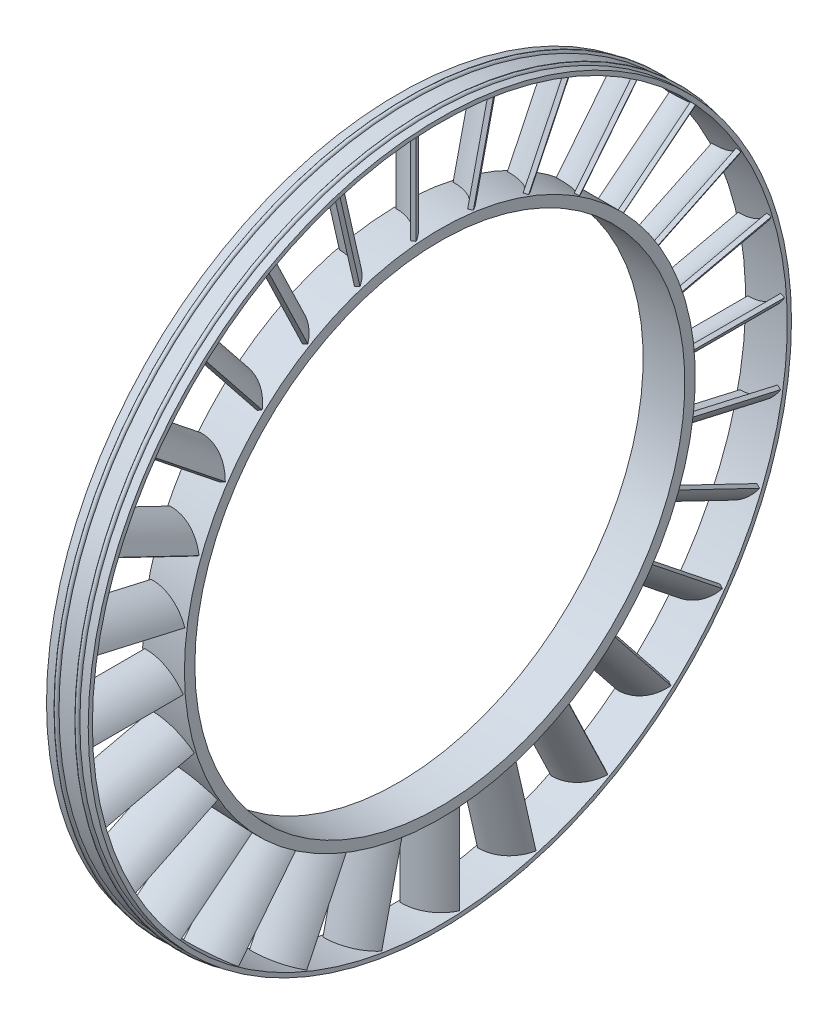
SolidWorks part; units mm, degrees
ref_plane "Front Plane" through (0, 0, 0) normal (0, 0, 1) x (1, 0, 0)
ref_plane "Top Plane" through (0, 0, 0) normal (0, 1, 0) x (1, 0, 0)
ref_plane "Right Plane" through (0, 0, 0) normal (1, 0, 0) x (0, 0, -1)
sketch "Sketch1" plane through (0, 0, 0) normal (0, 0, 1) x (1, 0, 0)
  line L0 (-31.8966, 0) -> (35.2586, 0) construction
  line L1 (0, 0) -> (0, 166.64) construction
  line L2 (-10, 122.5) -> (-10, 222.1214) construction
  line L3 (-10, 117.5) -> (10, 117.5)
  line L4 (-10, 117.5) -> (-10, 122.5)
  line L5 (-10, 122.5) -> (10, 122.5)
  line L6 (10, 117.5) -> (10, 122.5)
  line L7 (-10, 117.5) -> (10, 122.5) construction
  line L8 (-10, 122.5) -> (10, 117.5) construction
  line L9 (10, 122.5) -> (10, 224.5445) construction
  line L10 (0, 166.64) -> (0, 167.64) construction
  line L11 (-10, 166.64) -> (10, 166.64)
  line L12 (-10, 166.64) -> (-10, 168.64)
  line L13 (-10, 168.64) -> (-6, 168.64)
  line L14 (10, 166.64) -> (10, 168.64)
  line L16 (6, 168.64) -> (10, 168.64)
  line L17 (-4, 168.64) -> (4, 168.64)
  line L18 (0, 167.64) -> (0, 402.6081) construction
  arc A0 (6, 168.64) -> (4, 168.64) centre (5, 168.64) ccw
  arc A1 (-4, 168.64) -> (-6, 168.64) centre (-5, 168.64) ccw
  point P5 (0, 120)
  point P10 (0, 167.64)
  dimension "D6" = 2
  dimension "D7" = 2
  dimension "D1" = 5
  dimension "D2" = 20
  dimension "D3" = 117.5
  dimension "D4" = 166.64
  dimension "D5" = 2
  dimension "D8" = 5
  dimension "D9" = 5
revolve "Revolve1" add sketch "Sketch1" angle 360 about L0
sketch "Sketch2" plane through (0, 0, 0) normal (0, 1, 0) x (1, 0, 0)
  line L0 (-34.4479, 0) -> (35.693, 0) construction
  line L1 (10, -168.64) -> (10, 168.64) construction
  line L2 (-10, 168.64) -> (-10, -168.64) construction
  arc A0 (-9, 0) -> (9, -10.3721) centre (-8.5308, -19.9905) cw
  point P3 (-9, 0)
  point P4 (9, -10.3721)
  dimension "D1" = 1
  dimension "D2" = 1
extrude "Extrude-Thin1" add sketch "Sketch2" along normal up to surface (166.628 mm away) thin up to face at (10, 0, 166.64) thin type one direction wall 2
pattern_circular "CirPattern1" count 28 over 360 about axis through (-31.8966, 0, 0) along (-1, 0, 0) of "Extrude-Thin1"
sketch "Sketch3" plane through (0, 0, 0) normal (1, 0, 0) x (0, 0, -1)
  circle A0 centre (0, 0) radius 117.5
extrude "Cut-Extrude1" cut sketch "Sketch3" against normal mid plane 60
